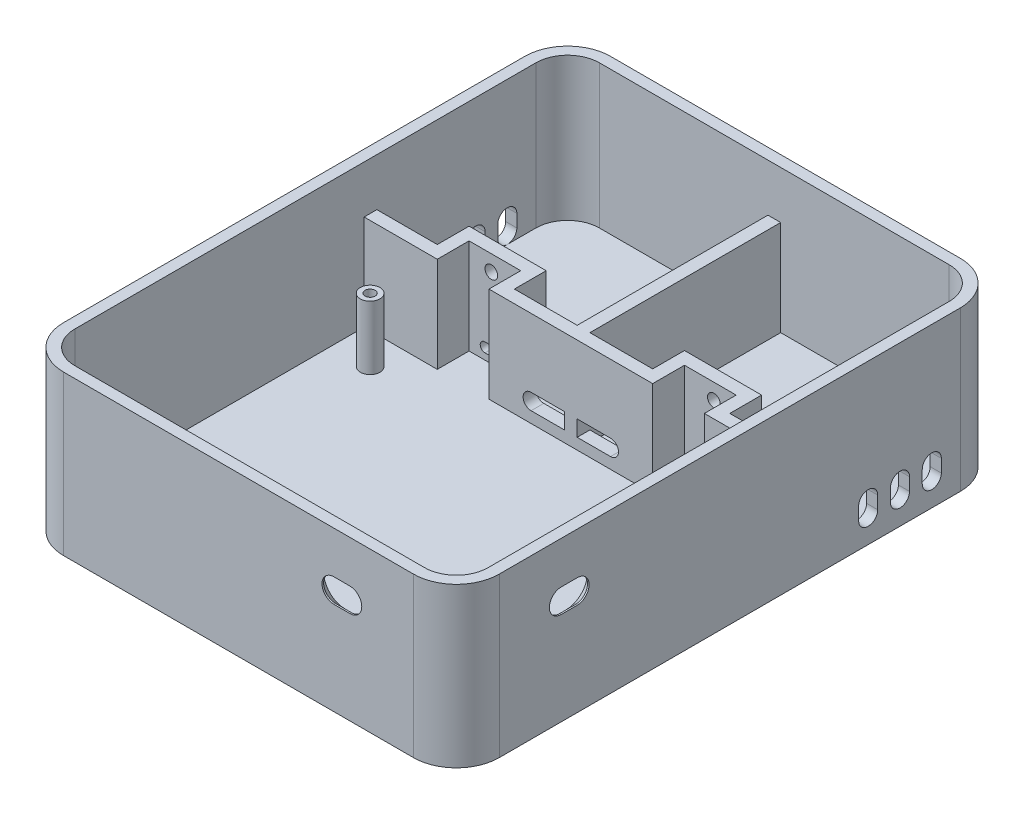
SolidWorks part; units mm, degrees
ref_plane "Front Plane" through (0, 0, 0) normal (0, 0, 1) x (1, 0, 0)
ref_plane "Top Plane" through (0, 0, 0) normal (0, 1, 0) x (1, 0, 0)
ref_plane "Right Plane" through (0, 0, 0) normal (1, 0, 0) x (0, 0, -1)
sketch "Sketch1" plane through (0, 0, 0) normal (0, 1, 0) x (1, 0, 0)
  line L1 (-55, -82.5) -> (55, -82.5)
  line L2 (-65, -72.5) -> (-65, 72.5)
  line L3 (-55, 82.5) -> (55, 82.5)
  line L4 (65, -72.5) -> (65, 72.5)
  line L5 (-65, -82.5) -> (65, 82.5) construction
  line L6 (-65, 82.5) -> (65, -82.5) construction
  line L18 (-68.5, -72.5) -> (-68.5, 72.5)
  line L19 (-55, 86) -> (55, 86)
  line L20 (68.5, -72.5) -> (68.5, 72.5)
  line L21 (-55, -86) -> (55, -86)
  arc A1 (55, -82.5) -> (65, -72.5) centre (55, -72.5) ccw
  arc A3 (-55, -82.5) -> (-65, -72.5) centre (-55, -72.5) cw
  arc A5 (55, 82.5) -> (65, 72.5) centre (55, 72.5) cw
  arc A7 (-65, 72.5) -> (-55, 82.5) centre (-55, 72.5) cw
  arc A8 (-68.5, 72.5) -> (-55, 86) centre (-55, 72.5) cw
  arc A9 (55, 86) -> (68.5, 72.5) centre (55, 72.5) cw
  arc A10 (55, -86) -> (68.5, -72.5) centre (55, -72.5) ccw
  arc A11 (-55, -86) -> (-68.5, -72.5) centre (-55, -72.5) cw
  point P0 (0, 0)
  dimension "D1" = 130
  dimension "D2" = 165
  dimension "3.5" = 3.5
extrude "Boss-Extrude1" add sketch "Sketch1" along normal blind 5 contours L2 A7 L3 A5 L4 A1 L1 A3
sketch "Sketch2" plane through (0, 5, 0) normal (0, 1, 0) x (1, 0, 0)
  line L0 (65, -72.5) -> (65, 72.5) construction
  line L1 (-65, 18.5) -> (-42, 18.5)
  line L2 (-65, 18.5) -> (-65, 22.5)
  line L3 (-65, 22.5) -> (-46, 22.5)
  line L4 (65, 18.5) -> (65, 22.5)
  line L5 (-55, 82.5) -> (55, 82.5) construction
  line L7 (-65, 72.5) -> (-65, -72.5) construction
  line L8 (55, 82.5) -> (-55, 82.5) construction
  line L9 (-46, 22.5) -> (-46, 32.5)
  line L10 (-46, 32.5) -> (-21.7485, 32.5)
  line L12 (-21.7485, 32.5) -> (-21.7485, 22.5)
  line L13 (-42, 18.5) -> (-42, 28.5)
  line L14 (-42, 28.5) -> (-25.7485, 28.5)
  line L15 (-25.7485, 28.5) -> (-25.7485, 18.5)
  line L19 (0, -2.75) -> (0, 2.75) construction
  line L20 (42, 18.5) -> (42, 28.5)
  line L21 (46, 22.5) -> (46, 32.5)
  line L22 (25.7485, 28.5) -> (25.7485, 18.5)
  line L23 (21.7485, 32.5) -> (21.7485, 22.5)
  line L24 (42, 28.5) -> (25.7485, 28.5)
  line L25 (46, 32.5) -> (21.7485, 32.5)
  line L26 (-25.7485, 18.5) -> (25.7485, 18.5)
  line L29 (-21.7485, 22.5) -> (21.7485, 22.5)
  line L30 (42, 18.5) -> (65, 18.5)
  line L33 (46, 22.5) -> (65, 22.5)
  point P0 (0, 20.5)
  point P14 (-121.5447, 62.9461)
  point P15 (-21.7485, 27.5)
  point P23 (-43.2515, 18.5)
  point P25 (-27, 18.5)
  dimension "D1" = 4
  dimension "D2" = 60
  dimension "D3" = 24.2515
  dimension "D4" = 50
  dimension "D5" = 4
  dimension "D6" = 64
  dimension "D7" = 4
  dimension "D8" = 4
  dimension "D9" = 19
extrude "Boss-Extrude2" add sketch "Sketch2" along normal blind 30
sketch "Sketch3" plane through (0, 0, -18.5) normal (0, 0, 1) x (1, 0, 0)
  line L0 (65, 35) -> (65, 5) construction
  line L2 (-12.5, 11) -> (12.5, 11) construction
  line L3 (0, 0) -> (0, 45) construction
  line L4 (-12.5, 13.5052) -> (12.5, 13.5052)
  line L5 (-12.5, 8.4948) -> (12.5, 8.4948)
  line L6 (-55, 5) -> (55, 5) construction
  line L7 (33, 8.4948) -> (37, 8.4948) construction
  line L8 (33, 9.9896) -> (37, 9.9896)
  line L9 (33, 7) -> (37, 7)
  line L10 (-33, 8.4948) -> (-37, 8.4948) construction
  line L11 (-33, 9.9896) -> (-37, 9.9896)
  line L12 (-33, 7) -> (-37, 7)
  line L14 (-55, 5) -> (55, 5) construction
  circle A0 centre (35, 30) radius 2
  circle A1 centre (-35, 30) radius 2
  arc A2 (-12.5, 13.5052) -> (-12.5, 8.4948) centre (-12.5, 11) ccw
  arc A3 (12.5, 8.4948) -> (12.5, 13.5052) centre (12.5, 11) ccw
  arc A4 (33, 9.9896) -> (33, 7) centre (33, 8.4948) ccw
  arc A5 (37, 7) -> (37, 9.9896) centre (37, 8.4948) ccw
  arc A6 (-33, 9.9896) -> (-33, 7) centre (-33, 8.4948) cw
  arc A7 (-37, 7) -> (-37, 9.9896) centre (-37, 8.4948) cw
  point P13 (0, 11)
  point P18 (35, 8.4948)
  point P27 (-35.4415, 35)
  point P30 (-35, 8.4948)
  dimension "D1" = 4
  dimension "D8" = 1.4948
  dimension "D2" = 30
  dimension "D3" = 25
  dimension "D4" = 25
  dimension "D5" = 6
  dimension "D6" = 4
  dimension "D7" = 2
extrude "Cut-Extrude1" cut sketch "Sketch3" against normal through all
extrude "Boss-Extrude3" add sketch "Sketch1<3>" along normal blind 50
sketch "Sketch1<3>" plane through (0, 0, 0) normal (0, 1, 0) x (1, 0, 0) same geometry as "Sketch1"
sketch "Sketch4" plane through (0, 0, 0) normal (0, 1, 0) x (1, 0, 0)
  line L0 (-55, -82.5) -> (55, -82.5) construction
  circle A2 centre (25.7888, -60.1026) radius 7.95
  circle A3 centre (0, -62.5) radius 7.95
  circle A4 centre (25.7888, -60.1026) radius 8.45
  circle A5 centre (0, -62.5) radius 8.45
  dimension "D3" = 15.9
  dimension "D2" = 25.9
  dimension "D4" = 20
  dimension "D1" = 0.5
sketch "Sketch6" plane through (0, 0, 0) normal (0, -1, 0) x (1, 0, 0)
  line L0 (0, 76.42) -> (0, -12.5) construction
  line L2 (-65, -18.5) -> (-42, -18.5) construction
  line B0 (57.1825, -12.5) -> (-57.1825, -12.5)
  line B1 (-57.1825, -12.5) -> (-57.1825, 76.42)
  line B2 (-57.1825, 76.42) -> (57.1825, 76.42)
  line B3 (57.1825, 76.42) -> (57.1825, -12.5)
  circle B4 centre (53.3725, 72.59) radius 1.5875
  circle B5 centre (-53.3075, -8.69) radius 1.5875
  circle B6 centre (-53.3075, 72.59) radius 1.5875
  circle B7 centre (53.3725, -8.69) radius 1.5875
  dimension "D1" = 6
sketch_block_instance "Block1-1"
sketch_block "Block1"
sketch "Sketch7" plane through (0, 5, 0) normal (0, 1, 0) x (1, 0, 0)
  circle A0 centre (53.3725, 8.69) radius 1.5875 construction
  circle A1 centre (-53.3075, 8.69) radius 1.5875 construction
  circle A3 centre (-53.3075, -72.59) radius 1.5875 construction
  circle A6 centre (53.3725, -72.59) radius 1.5875 construction
  circle A34 centre (-53.3075, -72.59) radius 1.5875
  circle A35 centre (53.3725, -72.59) radius 1.5875
  circle A36 centre (53.3725, 8.69) radius 1.5875
  circle A37 centre (-53.3075, 8.69) radius 1.5875
  circle A38 centre (-53.3075, -72.59) radius 3.0875
  circle A39 centre (53.3725, -72.59) radius 3.0875
  circle A40 centre (-53.3075, 8.69) radius 3.0875
  circle A41 centre (53.3725, 8.69) radius 3.0875
  dimension "D1" = 1.5
extrude "Boss-Extrude4" add sketch "Sketch7" along normal blind 20
sketch "Sketch8"
sketch_block_instance "Block2-1"
sketch_block "Block2"
sketch "Sketch9" plane through (0, 35, 0) normal (0, 1, 0) x (1, 0, 0)
  line L0 (-65, 18.5) -> (-42, 18.5) construction
  line L1 (-2, 86) -> (2, 86)
  line L2 (-2, 86) -> (-2, 18.5)
  line L3 (-2, 18.5) -> (2, 18.5)
  line L4 (2, 86) -> (2, 18.5)
  line L5 (-2, 86) -> (2, 18.5) construction
  line L6 (-2, 18.5) -> (2, 86) construction
  line L7 (55, 86) -> (-55, 86) construction
  line L8 (-46, 22.5) -> (-65, 22.5) construction
  point P0 (0, 52.25)
  point P7 (0, 0)
  dimension "D1" = 4
  dimension "D2" = 4
extrude "Boss-Extrude5" add sketch "Sketch9" against normal blind 30
sketch "Sketch11" plane through (-68.5, 0, 0) normal (-1, 0, 0) x (0, 0, 1)
  line L0 (-63.5222, 8) -> (-63.5222, 12) construction
  line L1 (-66.5222, 8) -> (-66.5222, 12)
  line L2 (-60.5222, 8) -> (-60.5222, 12)
  line L3 (-50.5222, 8) -> (-50.5222, 12)
  line L4 (-56.5222, 8) -> (-56.5222, 12)
  line L5 (-53.5222, 8) -> (-53.5222, 12) construction
  line L6 (-40.5222, 8) -> (-40.5222, 12)
  line L7 (-46.5222, 8) -> (-46.5222, 12)
  line L8 (-43.5222, 8) -> (-43.5222, 12) construction
  line L12 (-72.5, 0) -> (72.5, 0) construction
  arc A0 (-66.5222, 8) -> (-60.5222, 8) centre (-63.5222, 8) ccw
  arc A1 (-60.5222, 12) -> (-66.5222, 12) centre (-63.5222, 12) ccw
  arc A2 (-56.5222, 8) -> (-50.5222, 8) centre (-53.5222, 8) ccw
  arc A3 (-50.5222, 12) -> (-56.5222, 12) centre (-53.5222, 12) ccw
  arc A4 (-46.5222, 8) -> (-40.5222, 8) centre (-43.5222, 8) ccw
  arc A5 (-40.5222, 12) -> (-46.5222, 12) centre (-43.5222, 12) ccw
  point P2 (-63.5222, 10)
  point P11 (-53.5222, 10)
  point P18 (-43.5222, 10)
  dimension "D2" = 3
  dimension "D1" = 4
  dimension "D4" = 8
  dimension "D3" = 3
extrude "Cut-Extrude2" cut sketch "Sketch11" against normal blind 20
mirror "Mirror1" about plane through (2, 5, -86) normal (1, 0, 0) of "Cut-Extrude2"
sketch "Sketch12" plane through (68.5, 0, 0) normal (1, 0, 0) x (0, 0, -1)
  line L0 (-53, 33) -> (-48, 33) construction
  line L1 (-53, 36.75) -> (-48, 36.75)
  line L2 (-53, 29.25) -> (-48, 29.25)
  line L3 (-72.5, 50) -> (-72.5, 0) construction
  line L4 (-72.5, 5) -> (18.5, 5) construction
  arc A0 (-53, 36.75) -> (-53, 29.25) centre (-53, 33) ccw
  arc A1 (-48, 29.25) -> (-48, 36.75) centre (-48, 33) ccw
  point P2 (-50.5, 33)
  point P7 (-56.75, 33)
  point P8 (-44.25, 33)
  dimension "D2" = 7.5
  dimension "D1" = 12.5
  dimension "D3" = 22
  dimension "D4" = 28
extrude "Cut-Extrude3" cut sketch "Sketch12" against normal blind 10
chamfer "Chamfer1" distance 3 angle 45 4 edges at (65, 36.75, 50.5) (65, 33, 44.25) (65, 33, 56.75) (65, 29.25, 50.5)
sketch "Sketch13" plane through (0, 0, 0) normal (0, 0, 1) x (1, 0, 0)
  line L0 (30, 33) -> (35, 33) construction
  line L1 (30, 36.75) -> (35, 36.75)
  line L2 (30, 29.25) -> (35, 29.25)
  line L5 (55, 50) -> (55, 0) construction
  arc A0 (30, 36.75) -> (30, 29.25) centre (30, 33) ccw
  arc A1 (35, 29.25) -> (35, 36.75) centre (35, 33) ccw
  point P2 (32.5, 33)
  point P7 (26.25, 33)
  point P8 (38.75, 33)
  dimension "D2" = 7.5
  dimension "D1" = 12.5
  dimension "D3" = 20
extrude "Cut-Extrude4" cut sketch "Sketch13" along normal through all
chamfer "Chamfer2" distance 3 angle 45 4 edges at (32.5, 36.75, 82.5) (26.25, 33, 82.5) (38.75, 33, 82.5) (32.5, 29.25, 82.5)
